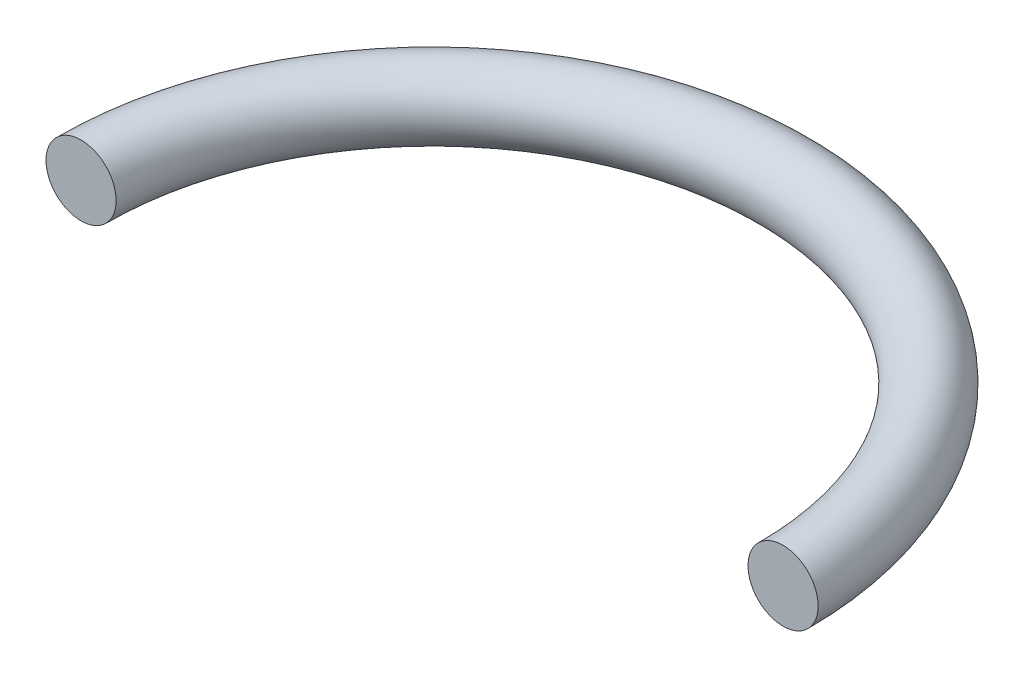
SolidWorks part; units mm, degrees
material "Acier inoxydable chromé"
ref_plane "Plan de face" through (0, 0, 0) normal (0, 0, 1) x (1, 0, 0)
ref_plane "Plan de dessus" through (0, 0, 0) normal (0, 1, 0) x (1, 0, 0)
ref_plane "Plan de droite" through (0, 0, 0) normal (1, 0, 0) x (0, 0, -1)
sketch "Esquisse1" plane through (0, 0, 0) normal (0, 0, 1) x (1, 0, 0)
  line L0 (-7.5, 0) -> (7.5, 0) construction
  line L1 (10.0447, 6) -> (-9.0388, 6) construction
  line L2 (0, -1.8531) -> (0, 46.4518) construction
  line L3 (-8.6802, 45) -> (10.0447, 45) construction
  circle A0 centre (7.5, 0) radius 0.7494
  dimension "D3" = 1.4988
  dimension "D1" = 6
  dimension "D2" = 45
  dimension "D4" = 15
sketch "Esquisse2" plane through (0, 0, 0) normal (0, 1, 0) x (1, 0, 0)
  circle A0 centre (0, 0) radius 7.5
curve "Hélice/Spirale1" pitch 6 height 45 turns 7.5
revolve "Révolution1" add sketch "Esquisse1" angle 180 about L2
ref_axis "Axe1" through (7.5, 0, 0) along (0, 0, 1)
ref_axis "Axe3" through (-7.5, 0, 0) along (0, 0, 1)
